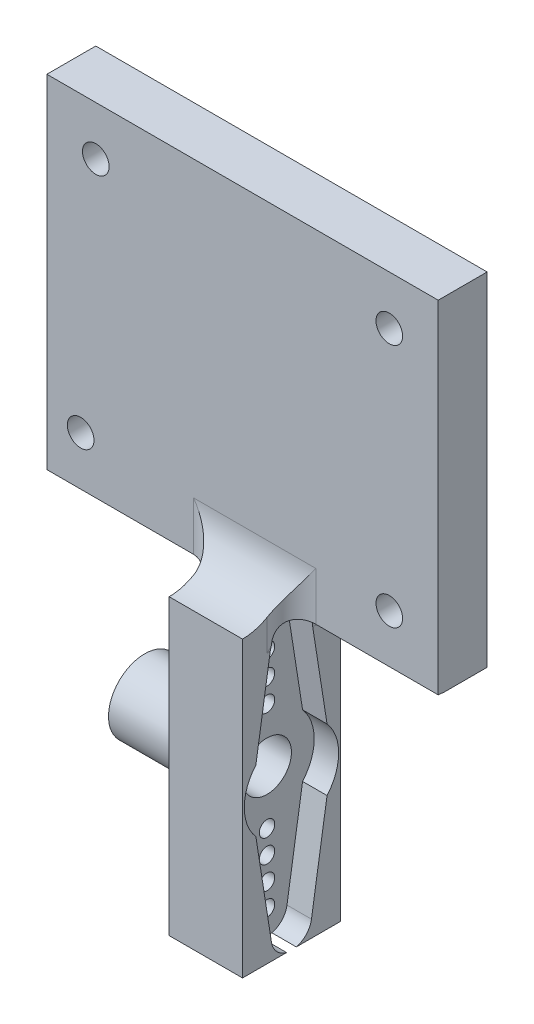
SolidWorks part; units mm, degrees
ref_plane "Front Plane" through (0, 0, 0) normal (0, 0, 1) x (1, 0, 0)
ref_plane "Top Plane" through (0, 0, 0) normal (0, 1, 0) x (1, 0, 0)
ref_plane "Right Plane" through (0, 0, 0) normal (1, 0, 0) x (0, 0, -1)
sketch "Sketch2" plane through (0, 0, 0) normal (1, 0, 0) x (0, 0, -1)
  line L0 (0, 0) -> (36.5165, 0) construction
  line L1 (-6.35, -19.05) -> (6.35, -19.05)
  line L2 (-6.35, -19.05) -> (-6.35, 19.05)
  line L3 (-6.35, 19.05) -> (6.35, 19.05)
  line L4 (6.35, -19.05) -> (6.35, 19.05)
  line L5 (-6.35, -19.05) -> (6.35, 19.05) construction
  line L6 (-6.35, 19.05) -> (6.35, -19.05) construction
  circle A0 centre (0, 0) radius 3.175
  point P0 (0, 0)
  dimension "D3" = 6.35
  dimension "D1" = 12.7
  dimension "D2" = 38.1
extrude "Boss-Extrude1" add sketch "Sketch2" along normal blind 9.525
sketch "Sketch3" plane through (0, 0, 0) normal (-1, 0, 0) x (0, 0, 1)
  circle A0 centre (0, 0) radius 4.699
  dimension "D1" = 9.398
extrude "Boss-Extrude2" add sketch "Sketch3" along normal blind 9.525
ref_plane "Plane1" through (3.175, 0, 0) normal (1, 0, 0) x (0, 0, -1)
sketch "Sketch6" plane through (3.175, 0, 0) normal (1, 0, 0) x (0, 0, -1)
  line L0 (6.35, 19.05) -> (-6.35, 19.05) construction
  line L1 (0, 19.05) -> (6.35, 19.05)
  line L2 (0, 19.05) -> (0, 63.5)
  line L3 (0, 63.5) -> (6.35, 63.5)
  line L4 (6.35, 19.05) -> (6.35, 63.5)
  dimension "D1" = 6.35
  dimension "D2" = 63.5
extrude "Boss-Extrude3" add sketch "Sketch6" along normal mid plane 50.8
fillet "Fillet1" radius 6.35 1 edges at (4.7625, 19.05, 0)
fillet "Fillet4" radius 3.175 4 edges at (0, 22.225, 0) (9.525, 22.225, 0) (9.525, 19.05, -3.175) (0, 19.05, -3.175)
sketch "Sketch7" plane through (9.525, 0, 0) normal (1, 0, 0) x (0, 0, -1)
  line L16 (2.5952, -16.9078) -> (4.6198, -4.0247)
  line L17 (-4.6197, -4.0247) -> (-2.5951, -16.9078)
  line L18 (-2.5951, 16.9078) -> (-4.6197, 4.0247)
  line L19 (4.6198, 4.0247) -> (2.5952, 16.9078)
  line L20 (2.5952, -16.9078) -> (4.6198, -4.0247)
  line L21 (-4.6197, -4.0247) -> (-2.5951, -16.9078)
  line L22 (-2.5951, 16.9078) -> (-4.6197, 4.0247)
  line L23 (4.6198, 4.0247) -> (2.5952, 16.9078)
  arc A16 (4.6198, -4.0247) -> (4.6198, 4.0247) centre (0, 0) ccw
  arc A17 (-2.5951, -16.9078) -> (2.5952, -16.9078) centre (0, -16.5) ccw
  arc A18 (-4.6197, 4.0247) -> (-4.6197, -4.0247) centre (0, 0) ccw
  arc A19 (2.5952, 16.9078) -> (-2.5951, 16.9078) centre (0, 16.5) ccw
  arc A20 (4.6198, -4.0247) -> (4.6198, 4.0247) centre (0, 0) ccw
  arc A21 (-2.5951, -16.9078) -> (2.5952, -16.9078) centre (0, -16.5) ccw
  arc A22 (-4.6197, 4.0247) -> (-4.6197, -4.0247) centre (0, 0) ccw
  arc A23 (2.5952, 16.9078) -> (-2.5951, 16.9078) centre (0, 16.5) ccw
  dimension "D1" = 0.127
sketch "Sketch8" plane through (9.525, 0, 0) normal (1, 0, 0) x (0, 0, -1)
  circle A0 centre (0, -16) radius 0.75 construction
  circle A3 centre (0, -13) radius 0.75 construction
  circle A4 centre (0, -10) radius 0.75 construction
  circle A5 centre (0, -7) radius 0.75 construction
  circle A6 centre (0, 16) radius 0.75 construction
  circle A7 centre (0, 13) radius 0.75 construction
  circle A8 centre (0, 10) radius 0.75 construction
  circle A9 centre (0, 7) radius 0.75 construction
  circle A10 centre (0, -16) radius 0.75 construction
  circle A11 centre (0, -13) radius 0.75 construction
  circle A12 centre (0, -10) radius 0.75 construction
  circle A13 centre (0, -7) radius 0.75 construction
  circle A14 centre (0, 16) radius 0.75 construction
  circle A15 centre (0, 13) radius 0.75 construction
  circle A16 centre (0, 10) radius 0.75 construction
  circle A17 centre (0, 7) radius 0.75 construction
  circle A18 centre (0, -16) radius 1.004
  circle A19 centre (0, -13) radius 1.004
  circle A20 centre (0, -10) radius 1.004
  circle A21 centre (0, -7) radius 1.004
  circle A22 centre (0, 16) radius 1.004
  circle A23 centre (0, 13) radius 1.004
  circle A24 centre (0, 10) radius 1.004
  circle A25 centre (0, 7) radius 1.004
extrude "Cut-Extrude1" cut sketch "Sketch7" against normal blind 3.175 and the other way through all
extrude "Cut-Extrude2" cut sketch "Sketch8" against normal through all
sketch "Sketch9" plane through (0, 0, -6.35) normal (0, 0, -1) x (-1, 0, 0)
  line L13 (15.875, 25.4) -> (15.875, 57.15)
  line L14 (3.175, 25.4) -> (15.875, 25.4)
  line L15 (-22.225, 25.4) -> (-12.7, 25.4)
  line L16 (-22.225, 57.15) -> (-22.225, 25.4)
  line L17 (15.875, 57.15) -> (-22.225, 57.15)
  line L18 (15.875, 25.4) -> (15.875, 57.15) construction
  line L19 (3.175, 25.4) -> (15.875, 25.4) construction
  line L20 (-22.225, 25.4) -> (-12.7, 25.4) construction
  line L21 (-22.225, 57.15) -> (-22.225, 25.4) construction
  line L22 (15.875, 57.15) -> (-22.225, 57.15) construction
  circle A0 centre (-22.225, 57.15) radius 1.727
  circle A1 centre (15.875, 57.15) radius 1.727
  circle A2 centre (17.8398, 25.4) radius 1.727
  circle A3 centre (-22.225, 25.4) radius 1.727
  dimension "D2" = 3.454
extrude "Cut-Extrude3" cut sketch "Sketch9" against normal through all
equation "\"tightTol\"= 0.005in"
equation "\"normTol\"= 0.01in"
equation "\"looseTol\"= 0.02in"
equation "\"Fry height\"= 0.5in"
equation "\"Fry spacing\"= 0.5625in"
equation "\"Potato width\"= \"Fry spacing\" * 4"
equation "\"Potato length\"= 3.5in"
equation "\"D1@Sketch3\"=0.375000in-\"tightTol\""
equation "\"Plate rim width\"= 0.5"
equation "\"D2@Sketch6\"=2.000000in+\"Plate rim width\""
equation "\"D1@Sketch8\"= \"normTol\""
equation "\"D2@Sketch9\"=3.2mm+\"normTol\""
